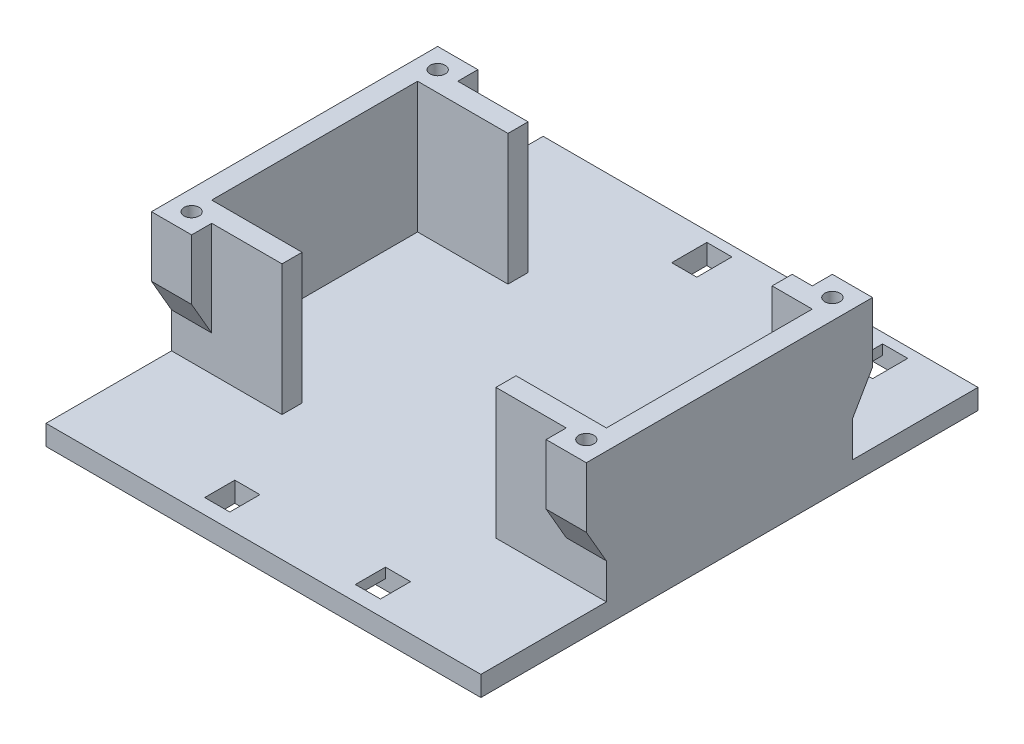
SolidWorks part; units mm, degrees
ref_plane "Front Plane" through (0, 0, 0) normal (0, 0, 1) x (1, 0, 0)
ref_plane "Top Plane" through (0, 0, 0) normal (0, 1, 0) x (1, 0, 0)
ref_plane "Right Plane" through (0, 0, 0) normal (1, 0, 0) x (0, 0, -1)
sketch "Sketch1" plane through (0, 0, 0) normal (0, 1, 0) x (1, 0, 0)
  line L0 (-0.2, 20.3) -> (39.1, 20.3)
  line L1 (0, 0) -> (38.9, 0) construction
  line L2 (0, 0) -> (0, 20.1) construction
  line L3 (0, 20.1) -> (38.9, 20.1) construction
  line L4 (38.9, 0) -> (38.9, 20.1) construction
  line L5 (39.1, -0.2) -> (39.1, 20.3)
  line L6 (-0.2, -0.2) -> (39.1, -0.2)
  line L7 (-0.2, -0.2) -> (-0.2, 20.3)
  line L8 (-2.2, 22.3) -> (41.1, 22.3)
  line L9 (41.1, -2.2) -> (41.1, 22.3)
  line L10 (-2.2, -2.2) -> (41.1, -2.2)
  line L11 (-2.2, -2.2) -> (-2.2, 22.3)
  line L13 (-2.2, -2.2) -> (41.1, -2.2)
  line L14 (-2.2, -2.2) -> (-2.2, -14.7)
  line L15 (-2.2, -14.7) -> (41.1, -14.7)
  line L16 (41.1, -2.2) -> (41.1, -14.7)
  line L17 (-2.2, 22.3) -> (41.1, 22.3)
  line L18 (-2.2, 22.3) -> (-2.2, 34.8)
  line L19 (-2.2, 34.8) -> (41.1, 34.8)
  line L20 (41.1, 22.3) -> (41.1, 34.8)
  dimension "D1" = 38.9
  dimension "D2" = 20.1
  dimension "D5" = 12.5
  dimension "D6" = 12.5
  dimension "D3" = 0.2
  dimension "D4" = 2
extrude "Boss-Extrude1" add sketch "Sketch1" along normal blind 2 contours L11 L10 L9 L8 L6 L7 L0 L5 | L7 L6 L5 L0 | L16 L10 L14 L15 | L8 L20 L19 L18 region at (19.45, 0, -10.05) region at (19.45, 0, -28.55) region at (19.45, 0, -21.8025) region at (19.45, 0, 8.45)
extrude "Boss-Extrude2" add sketch "Sketch1<3>" along normal blind 15 contours L11 L10 L9 L8 L6 L7 L0 L5 region at (19.45, 0, -21.8025)
sketch "Sketch1<3>" plane through (0, 0, 0) normal (0, 1, 0) x (1, 0, 0) same geometry as "Sketch1"
sketch "Sketch3" plane through (0, 15, 0) normal (0, 1, 0) x (1, 0, 0)
  line L1 (-2.2, -2.2) -> (1.8, -2.2)
  line L2 (-2.2, -2.2) -> (-2.2, -4.2)
  line L3 (-2.2, -4.2) -> (1.8, -4.2)
  line L4 (1.8, -2.2) -> (1.8, -4.2)
  line L5 (41.1, -2.2) -> (37.1, -2.2)
  line L6 (41.1, -2.2) -> (41.1, -4.2)
  line L7 (41.1, -4.2) -> (37.1, -4.2)
  line L8 (37.1, -2.2) -> (37.1, -4.2)
  line L9 (41.1, 22.3) -> (37.1, 22.3)
  line L10 (41.1, 22.3) -> (41.1, 24.3)
  line L11 (41.1, 24.3) -> (37.1, 24.3)
  line L12 (37.1, 22.3) -> (37.1, 24.3)
  line L13 (-2.2, 22.3) -> (1.8, 22.3)
  line L14 (-2.2, 22.3) -> (-2.2, 24.3)
  line L15 (-2.2, 24.3) -> (1.8, 24.3)
  line L16 (1.8, 22.3) -> (1.8, 24.3)
  dimension "D1" = 2
  dimension "D2" = 4
  dimension "D3" = 2
  dimension "D4" = 4
  dimension "D5" = 4
  dimension "D6" = 2
  dimension "D7" = 2
  dimension "D8" = 4
extrude "Boss-Extrude4" add sketch "Sketch3" against normal blind 6
chamfer "Chamfer2" distance 2 angle 60 4 edges at (-0.2, 9, -22.3) (39.1, 9, -22.3) (39.1, 9, 2.2) (-0.2, 9, 2.2) first distance on face at (-0.2, 9, -23.3) first distance on face at (39.1, 9, -23.3) first distance on face at (39.1, 9, 3.2) first distance on face at (-0.2, 9, 3.2)
sketch "Sketch4" plane through (0, 15, 0) normal (0, 1, 0) x (1, 0, 0)
  line L0 (41.1, -4.2) -> (41.1, 24.3) construction
  line L1 (37.1, -4.2) -> (41.1, -4.2) construction
  line L2 (-2.2, -4.2) -> (-2.2, 24.3) construction
  line L3 (-2.2, -4.2) -> (1.8, -4.2) construction
  line L4 (1.8, 24.3) -> (-2.2, 24.3) construction
  line L5 (41.1, 24.3) -> (37.1, 24.3) construction
  circle A0 centre (-0.2, 22.3) radius 0.75
  circle A1 centre (-0.2, -2.2) radius 0.75
  circle A2 centre (39.1, -2.2) radius 0.75
  circle A3 centre (39.1, 22.3) radius 0.75
  dimension "D1" = 1.5
  dimension "D2" = 1.5
  dimension "D3" = 1.5
  dimension "D4" = 1.5
  dimension "D5" = 2
  dimension "D6" = 2
  dimension "D7" = 2
  dimension "D8" = 2
  dimension "D9" = 2
  dimension "D10" = 2
  dimension "D11" = 2
  dimension "D12" = 2
extrude "Cut-Extrude1" cut sketch "Sketch4" against normal blind 5
sketch "Sketch5" plane through (0, 15, 0) normal (0, 1, 0) x (1, 0, 0)
  line L6 (1.8, 22.3) -> (37.1, 22.3) construction
  line L7 (8.8, 22.3) -> (35.1, 22.3)
  line L8 (8.8, 22.3) -> (8.8, 20.3)
  line L9 (8.8, 20.3) -> (35.1, 20.3)
  line L10 (35.1, 22.3) -> (35.1, 20.3)
  line L11 (-0.2, 20.3) -> (39.1, 20.3) construction
  line L12 (39.1, 20.3) -> (39.1, -0.2) construction
  line L13 (1.8, 22.3) -> (1.8, 24.3) construction
  line L14 (39.1, -0.2) -> (-0.2, -0.2) construction
  line L15 (8.8, -0.2) -> (30.1, -0.2)
  line L16 (8.8, -0.2) -> (8.8, -2.2)
  line L17 (8.8, -2.2) -> (30.1, -2.2)
  line L18 (30.1, -0.2) -> (30.1, -2.2)
  line L19 (1.8, -2.2) -> (37.1, -2.2) construction
  line L20 (-0.2, 20.3) -> (-0.2, -0.2) construction
  dimension "D1" = 4
  dimension "D2" = 7
  dimension "D3" = 9
  dimension "D4" = 9
extrude "Cut-Extrude2" cut sketch "Sketch5" against normal up to surface (13 mm away) up to face at (19.45, 2, -10.05)
sketch "Sketch7" plane through (0, 2, 0) normal (0, 1, 0) x (1, 0, 0)
  line L0 (-2.2, 34.8) -> (41.1, 34.8) construction
  line L1 (17.6, 33.8) -> (15.1, 33.8)
  line L2 (17.6, 33.8) -> (17.6, 30.3)
  line L3 (17.6, 30.3) -> (15.1, 30.3)
  line L4 (15.1, 33.8) -> (15.1, 30.3)
  line L5 (35.1, 33.8) -> (32.6, 33.8)
  line L6 (35.1, 33.8) -> (35.1, 30.3)
  line L7 (35.1, 30.3) -> (32.6, 30.3)
  line L8 (32.6, 33.8) -> (32.6, 30.3)
  line L9 (41.1, 22.3) -> (41.1, 34.8) construction
  line L10 (-2.2, -14.7) -> (41.1, -14.7) construction
  line L11 (12.1, -10.2) -> (14.6, -10.2)
  line L12 (12.1, -10.2) -> (12.1, -13.2)
  line L13 (12.1, -13.2) -> (14.6, -13.2)
  line L14 (14.6, -10.2) -> (14.6, -13.2)
  line L15 (29.6, -10.2) -> (27.1, -10.2)
  line L16 (29.6, -10.2) -> (29.6, -13.2)
  line L17 (29.6, -13.2) -> (27.1, -13.2)
  line L18 (27.1, -10.2) -> (27.1, -13.2)
  line L19 (41.1, -14.7) -> (41.1, -2.2) construction
  dimension "D1" = 3.5
  dimension "D2" = 3.5
  dimension "D3" = 2.5
  dimension "D4" = 2.5
  dimension "D5" = 15
  dimension "D6" = 1
  dimension "D7" = 6
  dimension "D8" = 2.5
  dimension "D9" = 3
  dimension "D10" = 2.5
  dimension "D11" = 3
  dimension "D12" = 12.5
  dimension "D13" = 1.5
  dimension "D14" = 14
extrude "Cut-Extrude3" cut sketch "Sketch7" against normal through all
sketch "Sketch8" plane through (0, 0, 0) normal (0, -1, 0) x (1, 0, 0)
  line L1 (32.6, -33.8) -> (17.6, -33.8)
  line L2 (32.6, -33.8) -> (32.6, -30.3)
  line L3 (32.6, -30.3) -> (17.6, -30.3)
  line L4 (17.6, -33.8) -> (17.6, -30.3)
  line L5 (27.1, 10.2) -> (14.6, 10.2)
  line L6 (27.1, 10.2) -> (27.1, 13.2)
  line L7 (27.1, 13.2) -> (14.6, 13.2)
  line L8 (14.6, 10.2) -> (14.6, 13.2)
extrude "Cut-Extrude4" cut sketch "Sketch8" against normal blind 1
sketch "Sketch9" plane through (0, 2, 0) normal (0, 1, 0) x (1, 0, 0)
  line L0 (8.8, 22.3) -> (-2.2, 22.3) construction
  line L1 (-1.2, 24.8) -> (1.8, 24.8)
  line L2 (-1.2, 24.8) -> (-1.2, 22.3)
  line L3 (-1.2, 22.3) -> (1.8, 22.3)
  line L4 (1.8, 24.8) -> (1.8, 22.3)
  line L5 (-2.2, 22.3) -> (-2.2, 34.8) construction
  point P6 (3.3, 22.3)
  dimension "D1" = 3
  dimension "D2" = 2.5
  dimension "D3" = 0
  dimension "D4" = 1
extrude "Cut-Extrude5" cut sketch "Sketch9" against normal through all
sketch "Sketch10" plane through (0, 0, 0) normal (0, -1, 0) x (1, 0, 0)
  line L0 (-2.2, -34.8) -> (41.1, -34.8) construction
  line L1 (-1.2, -24.8) -> (1.8, -24.8)
  line L2 (-1.2, -24.8) -> (-1.2, -34.8)
  line L3 (-1.2, -34.8) -> (1.8, -34.8)
  line L4 (1.8, -24.8) -> (1.8, -34.8)
  line L5 (1.8, -22.3) -> (1.8, -24.8) construction
extrude "Cut-Extrude6" cut sketch "Sketch10" against normal blind 1
